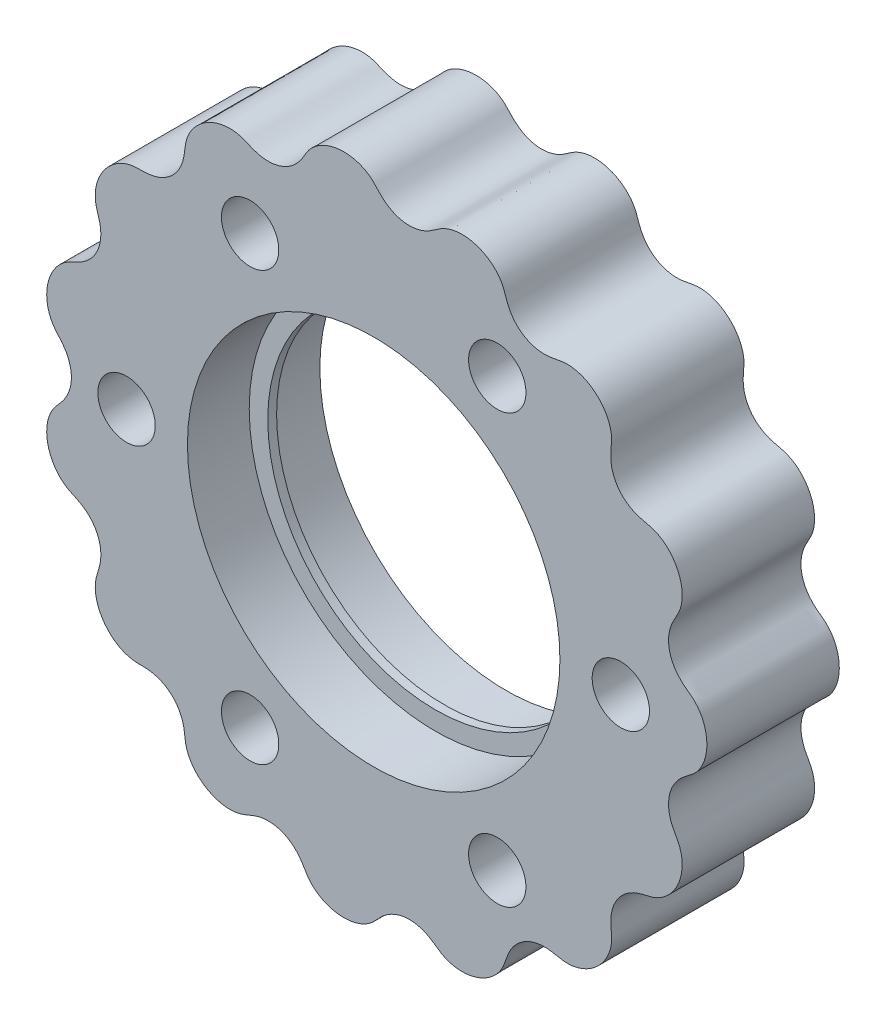
SolidWorks part; units mm, degrees
ref_plane "Front Plane" through (0, 0, 0) normal (0, 0, 1) x (1, 0, 0)
ref_plane "Top Plane" through (0, 0, 0) normal (0, 1, 0) x (1, 0, 0)
ref_plane "Right Plane" through (0, 0, 0) normal (1, 0, 0) x (0, 0, -1)
ref_axis "Axis1" through (0, 0, 55) along (0, 0, -1)
sketch "LobeBaseSketch" plane through (0, 0, 0) normal (0, 0, 1) x (1, 0, 0)
  spline S0 degree 3 poles (37.7454, -0.2739) (37.7523, 0) (37.7454, 0.2739) (37.725, 0.546) (37.6912, 0.8147) (37.6446, 1.0782) (37.5859, 1.3351) (37.516, 1.5838) (37.4359, 1.823) (37.3468, 2.0516) (37.2498, 2.2685) (37.1465, 2.473) (37.0381, 2.6645) (36.926, 2.8426) (36.8116, 3.0073) (36.6961, 3.1588) (36.5806, 3.2975) (36.4657, 3.4243) (36.352, 3.5402) (36.2393, 3.6469) (36.1268, 3.7462) (36.0127, 3.8409) (35.894, 3.9343) (35.7656, 4.0314) (35.62, 4.139) (35.4464, 4.2676) (35.2296, 4.4339) (34.9517, 4.6653) (34.5984, 5.0047) (34.1802, 5.5091) (33.7629, 6.222) (33.4654, 7.1133) (33.3747, 8.0485) (33.4659, 8.8695) (33.6428, 9.5004) (33.8275, 9.9542) (33.9873, 10.2786) (34.1177, 10.5187) (34.224, 10.7068) (34.3132, 10.8643) (34.391, 11.0052) (34.4615, 11.1389) (34.5272, 11.2718) (34.5896, 11.4083) (34.6491, 11.5515) (34.7059, 11.7037) (34.7592, 11.8662) (34.8084, 12.04) (34.8523, 12.2253) (34.8898, 12.4223) (34.9197, 12.6306) (34.9409, 12.8496) (34.9521, 13.0785) (34.9524, 13.3161) (34.9409, 13.5611) (34.9168, 13.8123) (34.8795, 14.0679) (34.8286, 14.3264) (34.764, 14.5861) (34.6855, 14.8453) (34.5936, 15.1023) (34.4884, 15.3552) (34.3708, 15.6026) (34.2414, 15.8429) (34.1013, 16.0746) (33.9515, 16.2965) (33.7934, 16.5072) (33.6284, 16.706) (33.4579, 16.892) (33.2835, 17.0645) (33.1067, 17.2233) (32.9291, 17.368) (32.7522, 17.4989) (32.5774, 17.616) (32.4059, 17.7199) (32.2388, 17.8113) (32.0768, 17.8911) (31.9203, 17.9602) (31.7693, 18.0198) (31.6229, 18.0714) (31.4798, 18.1164) (31.337, 18.1565) (31.1905, 18.1936) (31.0337, 18.23) (30.857, 18.2691) (30.6461, 18.316) (30.3805, 18.3797) (30.0324, 18.4781) (29.5716, 18.6445) (28.9844, 18.9351) (28.3133, 19.4168) (27.6789, 20.1099) (27.2157, 20.9274) (26.9651, 21.7145) (26.8701, 22.3628) (26.8542, 22.8525) (26.8682, 23.2139) (26.8897, 23.4862) (26.9103, 23.7013) (26.9278, 23.8815) (26.9415, 24.0418) (26.9515, 24.1926) (26.9575, 24.3407) (26.959, 24.4908) (26.9551, 24.6459) (26.9451, 24.808) (26.9277, 24.9782) (26.9019, 25.1569) (26.8666, 25.3441) (26.8208, 25.5393) (26.7634, 25.7418) (26.6936, 25.9505) (26.6108, 26.1641) (26.5145, 26.3813) (26.4043, 26.6005) (26.2801, 26.8201) (26.1421, 27.0384) (25.9904, 27.2539) (25.8257, 27.4649) (25.6487, 27.6698) (25.4601, 27.8671) (25.2612, 28.0554) (25.0531, 28.2336) (24.8372, 28.4005) (24.6149, 28.5551) (24.3879, 28.6969) (24.1577, 28.8251) (23.9261, 28.9396) (23.6947, 29.0402) (23.4652, 29.1268) (23.2392, 29.2) (23.0181, 29.26) (22.8032, 29.3075) (22.5959, 29.3434) (22.3969, 29.3686) (22.2071, 29.3842) (22.0266, 29.3911) (21.8556, 29.3906) (21.6933, 29.3837) (21.5387, 29.3713) (21.3896, 29.3541) (21.2429, 29.3327) (21.094, 29.307) (20.9359, 29.2765) (20.7586, 29.2404) (20.5468, 29.1974) (20.2782, 29.1476) (19.9203, 29.0958) (19.4316, 29.0604) (18.7769, 29.0871) (17.9679, 29.2541) (17.1065, 29.6293) (16.3508, 30.1878) (15.8017, 30.8049) (15.4512, 31.3585) (15.2376, 31.7994) (15.1034, 32.1352) (15.0122, 32.3928) (14.9436, 32.5976) (14.8863, 32.7693) (14.8336, 32.9214) (14.7814, 33.0632) (14.7266, 33.201) (14.6669, 33.3387) (14.6003, 33.4788) (14.5252, 33.6228) (14.4401, 33.7712) (14.3439, 33.924) (14.2355, 34.0806) (14.1142, 34.2403) (13.9795, 34.4019) (13.8308, 34.5642) (13.6683, 34.7257) (13.492, 34.8849) (13.3021, 35.0403) (13.0994, 35.1904) (12.8844, 35.3338) (12.6583, 35.469) (12.422, 35.5947) (12.1769, 35.7098) (11.9244, 35.8134) (11.6661, 35.9046) (11.4035, 35.9827) (11.1384, 36.0473) (10.8724, 36.0982) (10.6074, 36.1353) (10.3449, 36.1589) (10.0868, 36.1693) (9.8345, 36.167) (9.5896, 36.1529) (9.3533, 36.1277) (9.1269, 36.0926) (8.9113, 36.0487) (8.7073, 35.9971) (8.5153, 35.9392) (8.3355, 35.8762) (8.1679, 35.8092) (8.0118, 35.7391) (7.8664, 35.6668) (7.7302, 35.5926) (7.601, 35.5163) (7.4757, 35.437) (7.3501, 35.353) (7.2181, 35.2609) (7.0708, 35.1557) (6.8948, 35.0303) (6.6697, 34.8755) (6.3637, 34.6827) (5.9317, 34.4516) (5.3228, 34.2097) (4.5158, 34.0332) (3.5762, 34.0256) (2.6588, 34.2284) (1.9061, 34.5688) (1.3608, 34.932) (0.9863, 35.2479) (0.7271, 35.5001) (0.539, 35.6983) (0.393, 35.8575) (0.2708, 35.991) (0.1608, 36.1086) (0.0555, 36.2169) (-0.0506, 36.3205) (-0.1612, 36.422) (-0.279, 36.5229) (-0.4062, 36.6239) (-0.5443, 36.7248) (-0.6943, 36.8253) (-0.857, 36.9243) (-1.0328, 37.0209) (-1.2217, 37.1137) (-1.4234, 37.2015) (-1.6376, 37.2829) (-1.8634, 37.3566) (-2.1001, 37.4214) (-2.3464, 37.4761) (-2.601, 37.5196) (-2.8626, 37.5511) (-3.1296, 37.5699) (-3.4003, 37.5754) (-3.6731, 37.5673) (-3.9462, 37.5455) (-4.2178, 37.51) (-4.4863, 37.4612) (-4.75, 37.3996) (-5.0073, 37.3257) (-5.2566, 37.2405) (-5.4966, 37.145) (-5.7262, 37.0403) (-5.9442, 36.9277) (-6.1498, 36.8087) (-6.3423, 36.6845) (-6.5214, 36.5567) (-6.6868, 36.4266) (-6.8387, 36.2956) (-6.9773, 36.1649) (-7.1032, 36.0355) (-7.2172, 35.908) (-7.3206, 35.7828) (-7.4149, 35.6596) (-7.502, 35.5373) (-7.5842, 35.414) (-7.6647, 35.2861) (-7.7479, 35.1482) (-7.8396, 34.9922) (-7.9493, 34.8061) (-8.0921, 34.5732) (-8.2932, 34.2726) (-8.5938, 33.8857) (-9.0517, 33.4171) (-9.7172, 32.9276) (-10.5724, 32.5385) (-11.493, 32.3506) (-12.319, 32.3554) (-12.965, 32.4654) (-13.4356, 32.6017) (-13.775, 32.7267) (-14.0274, 32.8313) (-14.2255, 32.9173) (-14.3915, 32.9896) (-14.5397, 33.0523) (-14.6801, 33.1084) (-14.8191, 33.1598) (-14.9614, 33.2076) (-15.1101, 33.2519) (-15.2673, 33.2924) (-15.4345, 33.3284) (-15.6125, 33.3592) (-15.8014, 33.3834) (-16.0012, 33.4002) (-16.2115, 33.4081) (-16.4316, 33.4063) (-16.6603, 33.3936) (-16.8967, 33.369) (-17.1392, 33.332) (-17.3864, 33.2817) (-17.6367, 33.2179) (-17.8885, 33.1403) (-18.1401, 33.0489) (-18.3896, 32.9438) (-18.6355, 32.8254) (-18.8761, 32.6944) (-19.1099, 32.5516) (-19.3353, 32.3978) (-19.5511, 32.2342) (-19.7561, 32.0621) (-19.9492, 31.8828) (-20.1296, 31.6979) (-20.2967, 31.5089) (-20.4501, 31.3175) (-20.5895, 31.125) (-20.7149, 30.9333) (-20.8265, 30.7437) (-20.9248, 30.5576) (-21.0102, 30.3761) (-21.0836, 30.2004) (-21.146, 30.0309) (-21.1984, 29.8681) (-21.2419, 29.7116) (-21.2779, 29.5607) (-21.3077, 29.4136) (-21.3326, 29.2675) (-21.3542, 29.1179) (-21.3741, 28.9582) (-21.3945, 28.7783) (-21.419, 28.5637) (-21.4547, 28.2928) (-21.5161, 27.9364) (-21.6334, 27.4608) (-21.8611, 26.8463) (-22.2699, 26.1285) (-22.893, 25.4252) (-23.6576, 24.8791) (-24.4142, 24.5476) (-25.049, 24.3853) (-25.5343, 24.3184) (-25.8952, 24.2945) (-26.1683, 24.2874) (-26.3844, 24.2854) (-26.5653, 24.284) (-26.7263, 24.2809) (-26.8773, 24.2751) (-27.0252, 24.2655) (-27.1746, 24.2513) (-27.3285, 24.2313) (-27.4886, 24.2043) (-27.6561, 24.1693) (-27.8311, 24.1249) (-28.0136, 24.0703) (-28.2029, 24.0043) (-28.3983, 23.926) (-28.5985, 23.8348) (-28.8024, 23.7302) (-29.0083, 23.6117) (-29.2147, 23.4791) (-29.4202, 23.3327) (-29.6229, 23.1726) (-29.8214, 22.9993) (-30.014, 22.8134) (-30.1992, 22.6159) (-30.3757, 22.4078) (-30.5422, 22.1902) (-30.6977, 21.9646) (-30.8411, 21.7325) (-30.9717, 21.4952) (-31.0889, 21.2546) (-31.1924, 21.0124) (-31.282, 20.77) (-31.3578, 20.5294) (-31.4201, 20.2921) (-31.4691, 20.0596) (-31.5057, 19.8335) (-31.5306, 19.6148) (-31.5446, 19.4049) (-31.5489, 19.2044) (-31.5445, 19.0139) (-31.5325, 18.8338) (-31.5141, 18.6637) (-31.4903, 18.5031) (-31.4618, 18.3506) (-31.4291, 18.2041) (-31.3925, 18.0604) (-31.3514, 17.915) (-31.3046, 17.761) (-31.25, 17.5884) (-31.1851, 17.3823) (-31.1075, 17.1204) (-31.0187, 16.7698) (-30.9324, 16.2875) (-30.8905, 15.6336) (-30.972, 14.8116) (-31.2551, 13.9157) (-31.7315, 13.1058) (-32.2878, 12.4952) (-32.8018, 12.0887) (-33.218, 11.8302) (-33.5379, 11.6616) (-33.7845, 11.544) (-33.9811, 11.4544) (-34.1458, 11.3794) (-34.2916, 11.3111) (-34.4272, 11.2444) (-34.5585, 11.1755) (-34.6892, 11.1017) (-34.8216, 11.0209) (-34.9569, 10.9311) (-35.0956, 10.831) (-35.2375, 10.7193) (-35.3819, 10.5952) (-35.5281, 10.4578) (-35.6747, 10.3069) (-35.8206, 10.1421) (-35.9642, 9.9636) (-36.1041, 9.7716) (-36.2388, 9.5666) (-36.3669, 9.3492) (-36.487, 9.1205) (-36.5978, 8.8814) (-36.6982, 8.6333) (-36.7871, 8.3775) (-36.8637, 8.1156) (-36.9273, 7.8491) (-36.9775, 7.5798) (-37.0141, 7.3094) (-37.0369, 7.0396) (-37.0462, 6.7721) (-37.0422, 6.5086) (-37.0255, 6.2508) (-36.9969, 6.0002) (-36.9572, 5.7581) (-36.9075, 5.5257) (-36.8489, 5.3042) (-36.7827, 5.0944) (-36.7101, 4.8969) (-36.6324, 4.712) (-36.551, 4.5398) (-36.4668, 4.3801) (-36.3808, 4.2322) (-36.2937, 4.0952) (-36.2056, 3.9674) (-36.1162, 3.8469) (-36.0243, 3.7305) (-35.9276, 3.6144) (-35.8222, 3.4928) (-35.7022, 3.3573) (-35.5591, 3.1954) (-35.3816, 2.9877) (-35.1579, 2.7036) (-34.8829, 2.2981) (-34.5787, 1.7177) (-34.3188, 0.9336) (-34.213, 0) (-34.3188, -0.9336) (-34.5787, -1.7177) (-34.8829, -2.2981) (-35.1579, -2.7036) (-35.3816, -2.9877) (-35.5591, -3.1954) (-35.7022, -3.3573) (-35.8222, -3.4928) (-35.9276, -3.6144) (-36.0243, -3.7305) (-36.1162, -3.8469) (-36.2056, -3.9674) (-36.2937, -4.0952) (-36.3808, -4.2322) (-36.4668, -4.3801) (-36.551, -4.5398) (-36.6324, -4.712) (-36.7101, -4.8969) (-36.7827, -5.0944) (-36.8489, -5.3042) (-36.9075, -5.5257) (-36.9572, -5.7581) (-36.9969, -6.0002) (-37.0255, -6.2508) (-37.0422, -6.5086) (-37.0462, -6.7721) (-37.0369, -7.0396) (-37.0141, -7.3094) (-36.9775, -7.5798) (-36.9273, -7.8491) (-36.8637, -8.1156) (-36.7871, -8.3775) (-36.6982, -8.6333) (-36.5978, -8.8814) (-36.487, -9.1205) (-36.3669, -9.3492) (-36.2388, -9.5666) (-36.1041, -9.7716) (-35.9642, -9.9636) (-35.8206, -10.1421) (-35.6747, -10.3069) (-35.5281, -10.4578) (-35.3819, -10.5952) (-35.2375, -10.7193) (-35.0956, -10.831) (-34.9569, -10.9311) (-34.8216, -11.0209) (-34.6892, -11.1017) (-34.5585, -11.1755) (-34.4272, -11.2444) (-34.2916, -11.3111) (-34.1458, -11.3794) (-33.9811, -11.4544) (-33.7845, -11.544) (-33.5379, -11.6616) (-33.218, -11.8302) (-32.8018, -12.0887) (-32.2878, -12.4952) (-31.7315, -13.1058) (-31.2551, -13.9157) (-30.972, -14.8116) (-30.8905, -15.6336) (-30.9324, -16.2875) (-31.0187, -16.7698) (-31.1075, -17.1204) (-31.1851, -17.3823) (-31.25, -17.5884) (-31.3046, -17.761) (-31.3514, -17.915) (-31.3925, -18.0604) (-31.4291, -18.2041) (-31.4618, -18.3506) (-31.4903, -18.5031) (-31.5141, -18.6637) (-31.5325, -18.8338) (-31.5445, -19.0139) (-31.5489, -19.2044) (-31.5446, -19.4049) (-31.5306, -19.6148) (-31.5057, -19.8335) (-31.4691, -20.0596) (-31.4201, -20.2921) (-31.3578, -20.5294) (-31.282, -20.77) (-31.1924, -21.0124) (-31.0889, -21.2546) (-30.9717, -21.4952) (-30.8411, -21.7325) (-30.6977, -21.9646) (-30.5422, -22.1902) (-30.3757, -22.4078) (-30.1992, -22.6159) (-30.014, -22.8134) (-29.8214, -22.9993) (-29.6229, -23.1726) (-29.4202, -23.3327) (-29.2147, -23.4791) (-29.0083, -23.6117) (-28.8024, -23.7302) (-28.5985, -23.8348) (-28.3983, -23.926) (-28.2029, -24.0043) (-28.0136, -24.0703) (-27.8311, -24.1249) (-27.6561, -24.1693) (-27.4886, -24.2043) (-27.3285, -24.2313) (-27.1746, -24.2513) (-27.0252, -24.2655) (-26.8773, -24.2751) (-26.7263, -24.2809) (-26.5653, -24.284) (-26.3844, -24.2854) (-26.1683, -24.2874) (-25.8952, -24.2945) (-25.5343, -24.3184) (-25.049, -24.3853) (-24.4142, -24.5476) (-23.6576, -24.8791) (-22.893, -25.4252) (-22.2699, -26.1285) (-21.8611, -26.8463) (-21.6334, -27.4608) (-21.5161, -27.9364) (-21.4547, -28.2928) (-21.419, -28.5637) (-21.3945, -28.7783) (-21.3741, -28.9582) (-21.3542, -29.1179) (-21.3326, -29.2675) (-21.3077, -29.4136) (-21.2779, -29.5607) (-21.2419, -29.7116) (-21.1984, -29.8681) (-21.146, -30.0309) (-21.0836, -30.2004) (-21.0102, -30.3761) (-20.9248, -30.5576) (-20.8265, -30.7437) (-20.7149, -30.9333) (-20.5895, -31.125) (-20.4501, -31.3175) (-20.2967, -31.5089) (-20.1296, -31.6979) (-19.9492, -31.8828) (-19.7561, -32.0621) (-19.5511, -32.2342) (-19.3353, -32.3978) (-19.1099, -32.5516) (-18.8761, -32.6944) (-18.6355, -32.8254) (-18.3896, -32.9438) (-18.1401, -33.0489) (-17.8885, -33.1403) (-17.6367, -33.2179) (-17.3864, -33.2817) (-17.1392, -33.332) (-16.8967, -33.369) (-16.6603, -33.3936) (-16.4316, -33.4063) (-16.2115, -33.4081) (-16.0012, -33.4002) (-15.8014, -33.3834) (-15.6125, -33.3592) (-15.4345, -33.3284) (-15.2673, -33.2924) (-15.1101, -33.2519) (-14.9614, -33.2076) (-14.8191, -33.1598) (-14.6801, -33.1084) (-14.5397, -33.0523) (-14.3915, -32.9896) (-14.2255, -32.9173) (-14.0274, -32.8313) (-13.775, -32.7267) (-13.4356, -32.6017) (-12.965, -32.4654) (-12.319, -32.3554) (-11.493, -32.3506) (-10.5724, -32.5385) (-9.7172, -32.9276) (-9.0517, -33.4171) (-8.5938, -33.8857) (-8.2932, -34.2726) (-8.0921, -34.5732) (-7.9493, -34.8061) (-7.8396, -34.9922) (-7.7479, -35.1482) (-7.6647, -35.2861) (-7.5842, -35.414) (-7.502, -35.5373) (-7.4149, -35.6596) (-7.3206, -35.7828) (-7.2172, -35.908) (-7.1032, -36.0355) (-6.9773, -36.1649) (-6.8387, -36.2956) (-6.6868, -36.4266) (-6.5214, -36.5567) (-6.3423, -36.6845) (-6.1498, -36.8087) (-5.9442, -36.9277) (-5.7262, -37.0403) (-5.4966, -37.145) (-5.2566, -37.2405) (-5.0073, -37.3257) (-4.75, -37.3996) (-4.4863, -37.4612) (-4.2178, -37.51) (-3.9462, -37.5455) (-3.6731, -37.5673) (-3.4003, -37.5754) (-3.1296, -37.5699) (-2.8626, -37.5511) (-2.601, -37.5196) (-2.3464, -37.4761) (-2.1001, -37.4214) (-1.8634, -37.3566) (-1.6376, -37.2829) (-1.4234, -37.2015) (-1.2217, -37.1137) (-1.0328, -37.0209) (-0.857, -36.9243) (-0.6943, -36.8253) (-0.5443, -36.7248) (-0.4062, -36.6239) (-0.279, -36.5229) (-0.1612, -36.422) (-0.0506, -36.3205) (0.0555, -36.2169) (0.1608, -36.1086) (0.2708, -35.991) (0.393, -35.8575) (0.539, -35.6983) (0.7271, -35.5001) (0.9863, -35.2479) (1.3608, -34.932) (1.9061, -34.5688) (2.6588, -34.2284) (3.5762, -34.0256) (4.5158, -34.0332) (5.3228, -34.2097) (5.9317, -34.4516) (6.3637, -34.6827) (6.6697, -34.8755) (6.8948, -35.0303) (7.0708, -35.1557) (7.2181, -35.2609) (7.3501, -35.353) (7.4757, -35.437) (7.601, -35.5163) (7.7302, -35.5926) (7.8664, -35.6668) (8.0118, -35.7391) (8.1679, -35.8092) (8.3355, -35.8762) (8.5153, -35.9392) (8.7073, -35.9971) (8.9113, -36.0487) (9.1269, -36.0926) (9.3533, -36.1277) (9.5896, -36.1529) (9.8345, -36.167) (10.0868, -36.1693) (10.3449, -36.1589) (10.6074, -36.1353) (10.8724, -36.0982) (11.1384, -36.0473) (11.4035, -35.9827) (11.6661, -35.9046) (11.9244, -35.8134) (12.1769, -35.7098) (12.422, -35.5947) (12.6583, -35.469) (12.8844, -35.3338) (13.0994, -35.1904) (13.3021, -35.0403) (13.492, -34.8849) (13.6683, -34.7257) (13.8308, -34.5642) (13.9795, -34.4019) (14.1142, -34.2403) (14.2355, -34.0806) (14.3439, -33.924) (14.4401, -33.7712) (14.5252, -33.6228) (14.6003, -33.4788) (14.6669, -33.3387) (14.7266, -33.201) (14.7814, -33.0632) (14.8336, -32.9214) (14.8863, -32.7693) (14.9436, -32.5976) (15.0122, -32.3928) (15.1034, -32.1352) (15.2376, -31.7994) (15.4512, -31.3585) (15.8017, -30.8049) (16.3508, -30.1878) (17.1065, -29.6293) (17.9679, -29.2541) (18.7769, -29.0871) (19.4316, -29.0604) (19.9203, -29.0958) (20.2782, -29.1476) (20.5468, -29.1974) (20.7586, -29.2404) (20.9359, -29.2765) (21.094, -29.307) (21.2429, -29.3327) (21.3896, -29.3541) (21.5387, -29.3713) (21.6933, -29.3837) (21.8556, -29.3906) (22.0266, -29.3911) (22.2071, -29.3842) (22.3969, -29.3686) (22.5959, -29.3434) (22.8032, -29.3075) (23.0181, -29.26) (23.2392, -29.2) (23.4652, -29.1268) (23.6947, -29.0402) (23.9261, -28.9396) (24.1577, -28.8251) (24.3879, -28.6969) (24.6149, -28.5551) (24.8372, -28.4005) (25.0531, -28.2336) (25.2612, -28.0554) (25.4601, -27.8671) (25.6487, -27.6698) (25.8257, -27.4649) (25.9904, -27.2539) (26.1421, -27.0384) (26.2801, -26.8201) (26.4043, -26.6005) (26.5145, -26.3813) (26.6108, -26.1641) (26.6936, -25.9505) (26.7634, -25.7418) (26.8208, -25.5393) (26.8666, -25.3441) (26.9019, -25.1569) (26.9277, -24.9782) (26.9451, -24.808) (26.9551, -24.6459) (26.959, -24.4908) (26.9575, -24.3407) (26.9515, -24.1926) (26.9415, -24.0418) (26.9278, -23.8815) (26.9103, -23.7013) (26.8897, -23.4862) (26.8682, -23.2139) (26.8542, -22.8525) (26.8701, -22.3628) (26.9651, -21.7145) (27.2157, -20.9274) (27.6789, -20.1099) (28.3133, -19.4168) (28.9844, -18.9351) (29.5716, -18.6445) (30.0324, -18.4781) (30.3805, -18.3797) (30.6461, -18.316) (30.857, -18.2691) (31.0337, -18.23) (31.1905, -18.1936) (31.337, -18.1565) (31.4798, -18.1164) (31.6229, -18.0714) (31.7693, -18.0198) (31.9203, -17.9602) (32.0768, -17.8911) (32.2388, -17.8113) (32.4059, -17.7199) (32.5774, -17.616) (32.7522, -17.4989) (32.9291, -17.368) (33.1067, -17.2233) (33.2835, -17.0645) (33.4579, -16.892) (33.6284, -16.706) (33.7934, -16.5072) (33.9515, -16.2965) (34.1013, -16.0746) (34.2414, -15.8429) (34.3708, -15.6026) (34.4884, -15.3552) (34.5936, -15.1023) (34.6855, -14.8453) (34.764, -14.5861) (34.8286, -14.3264) (34.8795, -14.0679) (34.9168, -13.8123) (34.9409, -13.5611) (34.9524, -13.3161) (34.9521, -13.0785) (34.9409, -12.8496) (34.9197, -12.6306) (34.8898, -12.4223) (34.8523, -12.2253) (34.8084, -12.04) (34.7592, -11.8662) (34.7059, -11.7037) (34.6491, -11.5515) (34.5896, -11.4083) (34.5272, -11.2718) (34.4615, -11.1389) (34.391, -11.0052) (34.3132, -10.8643) (34.224, -10.7068) (34.1177, -10.5187) (33.9873, -10.2786) (33.8275, -9.9542) (33.6428, -9.5004) (33.4659, -8.8695) (33.3747, -8.0485) (33.4654, -7.1133) (33.7629, -6.222) (34.1802, -5.5091) (34.5984, -5.0047) (34.9517, -4.6653) (35.2296, -4.4339) (35.4464, -4.2676) (35.62, -4.139) (35.7656, -4.0314) (35.894, -3.9343) (36.0127, -3.8409) (36.1268, -3.7462) (36.2393, -3.6469) (36.352, -3.5402) (36.4657, -3.4243) (36.5806, -3.2975) (36.6961, -3.1588) (36.8116, -3.0073) (36.926, -2.8426) (37.0381, -2.6645) (37.1465, -2.473) (37.2498, -2.2685) (37.3468, -2.0516) (37.4359, -1.823) (37.516, -1.5838) (37.5859, -1.3351) (37.6446, -1.0782) (37.6912, -0.8147) (37.725, -0.546) (37.7454, -0.2739) (37.7523, 0) (37.7454, 0.2739) knots -0.003173 -0.002122 -0.001063 0 0.001063 0.002122 0.003173 0.004211 0.005233 0.006236 0.007215 0.008167 0.009088 0.009977 0.01083 0.011646 0.012424 0.013162 0.013861 0.014523 0.015151 0.01575 0.016327 0.016896 0.017473 0.018085 0.018768 0.019578 0.020598 0.021945 0.023783 0.026289 0.029543 0.033333 0.037124 0.040378 0.042884 0.044721 0.046069 0.047088 0.047899 0.048582 0.049193 0.049771 0.050339 0.050917 0.051516 0.052144 0.052805 0.053505 0.054243 0.05502 0.055836 0.05669 0.057578 0.0585 0.059452 0.060431 0.061433 0.062456 0.063494 0.064545 0.065604 0.066667 0.06773 0.068789 0.069839 0.070878 0.0719 0.072903 0.073881 0.074833 0.075755 0.076644 0.077497 0.078313 0.07909 0.079829 0.080528 0.08119 0.081817 0.082416 0.082994 0.083563 0.08414 0.084752 0.085435 0.086245 0.087264 0.088612 0.090449 0.092955 0.09621 0.1 0.10379 0.107045 0.109551 0.111388 0.112736 0.113755 0.114565 0.115248 0.11586 0.116437 0.117006 0.117584 0.118183 0.11881 0.119472 0.120171 0.12091 0.121687 0.122503 0.123356 0.124245 0.125167 0.126119 0.127097 0.1281 0.129122 0.130161 0.131211 0.13227 0.133333 0.134396 0.135455 0.136506 0.137544 0.138567 0.139569 0.140548 0.1415 0.142422 0.14331 0.144164 0.14498 0.145757 0.146495 0.147195 0.147856 0.148484 0.149083 0.149661 0.150229 0.150807 0.151418 0.152101 0.152912 0.153931 0.155279 0.157116 0.159622 0.162876 0.166667 0.170457 0.173711 0.176217 0.178055 0.179402 0.180422 0.181232 0.181915 0.182527 0.183104 0.183673 0.18425 0.184849 0.185477 0.186139 0.186838 0.187576 0.188354 0.18917 0.190023 0.190912 0.191833 0.192785 0.193764 0.194767 0.195789 0.196827 0.197878 0.198937 0.2 0.201063 0.202122 0.203173 0.204211 0.205233 0.206236 0.207215 0.208167 0.209088 0.209977 0.21083 0.211646 0.212424 0.213162 0.213861 0.214523 0.215151 0.21575 0.216327 0.216896 0.217473 0.218085 0.218768 0.219578 0.220598 0.221945 0.223783 0.226289 0.229543 0.233333 0.237124 0.240378 0.242884 0.244721 0.246069 0.247088 0.247899 0.248582 0.249193 0.249771 0.250339 0.250917 0.251516 0.252144 0.252805 0.253505 0.254243 0.25502 0.255836 0.25669 0.257578 0.2585 0.259452 0.260431 0.261433 0.262456 0.263494 0.264545 0.265604 0.266667 0.26773 0.268789 0.269839 0.270878 0.2719 0.272903 0.273881 0.274833 0.275755 0.276644 0.277497 0.278313 0.27909 0.279829 0.280528 0.28119 0.281817 0.282416 0.282994 0.283563 0.28414 0.284752 0.285435 0.286245 0.287264 0.288612 0.290449 0.292955 0.29621 0.3 0.30379 0.307045 0.309551 0.311388 0.312736 0.313755 0.314565 0.315248 0.31586 0.316437 0.317006 0.317584 0.318183 0.31881 0.319472 0.320171 0.32091 0.321687 0.322503 0.323356 0.324245 0.325167 0.326119 0.327097 0.3281 0.329122 0.330161 0.331211 0.33227 0.333333 0.334396 0.335455 0.336506 0.337544 0.338567 0.339569 0.340548 0.3415 0.342422 0.34331 0.344164 0.34498 0.345757 0.346495 0.347195 0.347856 0.348484 0.349083 0.349661 0.350229 0.350807 0.351418 0.352101 0.352912 0.353931 0.355279 0.357116 0.359622 0.362876 0.366667 0.370457 0.373711 0.376217 0.378055 0.379402 0.380422 0.381232 0.381915 0.382527 0.383104 0.383673 0.38425 0.384849 0.385477 0.386139 0.386838 0.387576 0.388354 0.38917 0.390023 0.390912 0.391833 0.392785 0.393764 0.394767 0.395789 0.396827 0.397878 0.398937 0.4 0.401063 0.402122 0.403173 0.404211 0.405233 0.406236 0.407215 0.408167 0.409088 0.409977 0.41083 0.411646 0.412424 0.413162 0.413861 0.414523 0.415151 0.41575 0.416327 0.416896 0.417473 0.418085 0.418768 0.419578 0.420598 0.421945 0.423783 0.426289 0.429543 0.433333 0.437124 0.440378 0.442884 0.444721 0.446069 0.447088 0.447899 0.448582 0.449193 0.449771 0.450339 0.450917 0.451516 0.452144 0.452805 0.453505 0.454243 0.45502 0.455836 0.45669 0.457578 0.4585 0.459452 0.460431 0.461433 0.462456 0.463494 0.464545 0.465604 0.466667 0.46773 0.468789 0.469839 0.470878 0.4719 0.472903 0.473881 0.474833 0.475755 0.476644 0.477497 0.478313 0.47909 0.479829 0.480528 0.48119 0.481817 0.482416 0.482994 0.483563 0.48414 0.484752 0.485435 0.486245 0.487264 0.488612 0.490449 0.492955 0.49621 0.5 0.50379 0.507045 0.509551 0.511388 0.512736 0.513755 0.514565 0.515248 0.51586 0.516437 0.517006 0.517584 0.518183 0.51881 0.519472 0.520171 0.52091 0.521687 0.522503 0.523356 0.524245 0.525167 0.526119 0.527097 0.5281 0.529122 0.530161 0.531211 0.53227 0.533333 0.534396 0.535455 0.536506 0.537544 0.538567 0.539569 0.540548 0.5415 0.542422 0.54331 0.544164 0.54498 0.545757 0.546495 0.547195 0.547856 0.548484 0.549083 0.549661 0.550229 0.550807 0.551418 0.552101 0.552912 0.553931 0.555279 0.557116 0.559622 0.562876 0.566667 0.570457 0.573711 0.576217 0.578055 0.579402 0.580422 0.581232 0.581915 0.582527 0.583104 0.583673 0.58425 0.584849 0.585477 0.586139 0.586838 0.587576 0.588354 0.58917 0.590023 0.590912 0.591833 0.592785 0.593764 0.594767 0.595789 0.596827 0.597878 0.598937 0.6 0.601063 0.602122 0.603173 0.604211 0.605233 0.606236 0.607215 0.608167 0.609088 0.609977 0.61083 0.611646 0.612424 0.613162 0.613861 0.614523 0.615151 0.61575 0.616327 0.616896 0.617473 0.618085 0.618768 0.619578 0.620598 0.621945 0.623783 0.626289 0.629543 0.633333 0.637124 0.640378 0.642884 0.644721 0.646069 0.647088 0.647899 0.648582 0.649193 0.649771 0.650339 0.650917 0.651516 0.652144 0.652805 0.653505 0.654243 0.65502 0.655836 0.65669 0.657578 0.6585 0.659452 0.660431 0.661433 0.662456 0.663494 0.664545 0.665604 0.666667 0.66773 0.668789 0.669839 0.670878 0.6719 0.672903 0.673881 0.674833 0.675755 0.676644 0.677497 0.678313 0.67909 0.679829 0.680528 0.68119 0.681817 0.682416 0.682994 0.683563 0.68414 0.684752 0.685435 0.686245 0.687264 0.688612 0.690449 0.692955 0.69621 0.7 0.70379 0.707045 0.709551 0.711388 0.712736 0.713755 0.714565 0.715248 0.71586 0.716437 0.717006 0.717584 0.718183 0.71881 0.719472 0.720171 0.72091 0.721687 0.722503 0.723356 0.724245 0.725167 0.726119 0.727097 0.7281 0.729122 0.730161 0.731211 0.73227 0.733333 0.734396 0.735455 0.736506 0.737544 0.738567 0.739569 0.740548 0.7415 0.742422 0.74331 0.744164 0.74498 0.745757 0.746495 0.747195 0.747856 0.748484 0.749083 0.749661 0.750229 0.750807 0.751418 0.752101 0.752912 0.753931 0.755279 0.757116 0.759622 0.762876 0.766667 0.770457 0.773711 0.776217 0.778055 0.779402 0.780422 0.781232 0.781915 0.782527 0.783104 0.783673 0.78425 0.784849 0.785477 0.786139 0.786838 0.787576 0.788354 0.78917 0.790023 0.790912 0.791833 0.792785 0.793764 0.794767 0.795789 0.796827 0.797878 0.798937 0.8 0.801063 0.802122 0.803173 0.804211 0.805233 0.806236 0.807215 0.808167 0.809088 0.809977 0.81083 0.811646 0.812424 0.813162 0.813861 0.814523 0.815151 0.81575 0.816327 0.816896 0.817473 0.818085 0.818768 0.819578 0.820598 0.821945 0.823783 0.826289 0.829543 0.833333 0.837124 0.840378 0.842884 0.844721 0.846069 0.847088 0.847899 0.848582 0.849193 0.849771 0.850339 0.850917 0.851516 0.852144 0.852805 0.853505 0.854243 0.85502 0.855836 0.85669 0.857578 0.8585 0.859452 0.860431 0.861433 0.862456 0.863494 0.864545 0.865604 0.866667 0.86773 0.868789 0.869839 0.870878 0.8719 0.872903 0.873881 0.874833 0.875755 0.876644 0.877497 0.878313 0.87909 0.879829 0.880528 0.88119 0.881817 0.882416 0.882994 0.883563 0.88414 0.884752 0.885435 0.886245 0.887264 0.888612 0.890449 0.892955 0.89621 0.9 0.90379 0.907045 0.909551 0.911388 0.912736 0.913755 0.914565 0.915248 0.91586 0.916437 0.917006 0.917584 0.918183 0.91881 0.919472 0.920171 0.92091 0.921687 0.922503 0.923356 0.924245 0.925167 0.926119 0.927097 0.9281 0.929122 0.930161 0.931211 0.93227 0.933333 0.934396 0.935455 0.936506 0.937544 0.938567 0.939569 0.940548 0.9415 0.942422 0.94331 0.944164 0.94498 0.945757 0.946495 0.947195 0.947856 0.948484 0.949083 0.949661 0.950229 0.950807 0.951418 0.952101 0.952912 0.953931 0.955279 0.957116 0.959622 0.962876 0.966667 0.970457 0.973711 0.976217 0.978055 0.979402 0.980422 0.981232 0.981915 0.982527 0.983104 0.983673 0.98425 0.984849 0.985477 0.986139 0.986838 0.987576 0.988354 0.98917 0.990023 0.990912 0.991833 0.992785 0.993764 0.994767 0.995789 0.996827 0.997878 0.998937 1 1.001063 1.002122 1.003173 only from (37.75, 0) to (37.75, 0)
extrude "LobeBase" add sketch "LobeBaseSketch" along normal blind 7.5 and the other way blind 7.5
sketch "AuxiliarySketchCycloidal01" plane through (0, 0, 0) normal (0, 0, 1) x (1, 0, 0)
  circle A0 centre (0, 0) radius 37.5 construction
  circle A1 centre (40, 0) radius 2.5 construction
  circle A2 centre (0, 0) radius 40 construction
  circle A3 centre (40, 0) radius 4 construction
  circle A4 centre (41.75, 0) radius 0.4 construction
  spline S0 degree 3 poles (41.75, 0) (41.75, 0.3159) (41.7263, 0.7888) (41.6479, 1.4126) (41.5667, 1.8721) (41.4639, 2.3223) (41.3406, 2.7608) (41.1984, 3.1856) (41.0387, 3.5951) (40.8634, 3.9874) (40.6745, 4.3612) (40.474, 4.7152) (40.2644, 5.0486) (40.0478, 5.3606) (39.8266, 5.6507) (39.6034, 5.9189) (39.3805, 6.1651) (39.1603, 6.3899) (38.9452, 6.5937) (38.7375, 6.7776) (38.5391, 6.9426) (38.3523, 7.0901) (38.1787, 7.2217) (38.0199, 7.3392) (37.8775, 7.4445) (37.7524, 7.5398) (37.6456, 7.6272) (37.5575, 7.7094) (37.4887, 7.7889) (37.4394, 7.8689) (37.4107, 7.9519) (37.4032, 8.0394) (37.4157, 8.1325) (37.4462, 8.2332) (37.4932, 8.344) (37.5552, 8.4674) (37.6307, 8.6052) (37.7181, 8.7594) (37.8153, 8.9313) (37.9204, 9.1221) (38.0311, 9.3329) (38.1451, 9.5643) (38.2601, 9.8168) (38.3737, 10.0905) (38.4835, 10.3854) (38.5869, 10.701) (38.6818, 11.0368) (38.7658, 11.3918) (38.8368, 11.7649) (38.8927, 12.1547) (38.9318, 12.5597) (38.9524, 12.978) (38.9529, 13.4077) (38.9323, 13.8467) (38.8895, 14.2927) (38.8237, 14.7434) (38.7346, 15.1964) (38.6218, 15.6493) (38.4397, 16.2511) (38.269, 16.6926) (38.1405, 16.9813) knots 0 0 0 0 0.050201 0.075134 0.099868 0.124338 0.148477 0.172224 0.195514 0.218287 0.240484 0.262046 0.282919 0.303048 0.322383 0.340875 0.358479 0.375153 0.390859 0.405563 0.419235 0.431851 0.443394 0.453855 0.463234 0.471549 0.478837 0.485168 0.490661 0.49551 0.5 0.50449 0.509339 0.514832 0.521163 0.528451 0.536766 0.546145 0.556606 0.568149 0.580765 0.594437 0.609141 0.624847 0.641521 0.659125 0.677617 0.696952 0.717081 0.737954 0.759516 0.781713 0.804486 0.827776 0.851523 0.875662 0.900132 0.924866 0.949799 1 1 1 1 construction
sketch "Sketch4" plane through (0, 0, 7.5) normal (0, 0, 1) x (1, 0, 0)
  circle A0 centre (0, 0) radius 21.1
  dimension "D1" = 42.2
extrude "Cut-Extrude1" cut sketch "Sketch4" against normal blind 7
sketch "Sketch5" plane through (0, 0, -7.5) normal (0, 0, -1) x (-1, 0, 0)
  circle A0 centre (0, 0) radius 21.1
  dimension "D1" = 42.2
extrude "Cut-Extrude2" cut sketch "Sketch5" against normal blind 7
sketch "Sketch6" plane through (0, 0, -7.5) normal (0, 0, -1) x (-1, 0, 0)
  circle A0 centre (0, 0) radius 19
  dimension "D1" = 38
extrude "Cut-Extrude3" cut sketch "Sketch6" against normal through all
sketch "Sketch7" plane through (0, 0, -7.5) normal (0, 0, -1) x (-1, 0, 0)
  circle A0 centre (0, 0) radius 28 construction
  circle A1 centre (-28, 0) radius 4.1
  dimension "D1" = 56
  dimension "D2" = 8.2
extrude "Cut-Extrude4" cut sketch "Sketch7" against normal blind 5
sketch "Sketch8" plane through (0, 0, -7.5) normal (0, 0, -1) x (-1, 0, 0)
  circle A0 centre (-28, 0) radius 3.25
  dimension "D1" = 6.5
extrude "Cut-Extrude5" cut sketch "Sketch8" against normal blind 32
pattern_circular "CirPattern1" count 6 over 360 about axis through (0, 0, -7.5) along (0, 0, -1) of "Cut-Extrude5", "Cut-Extrude4"
